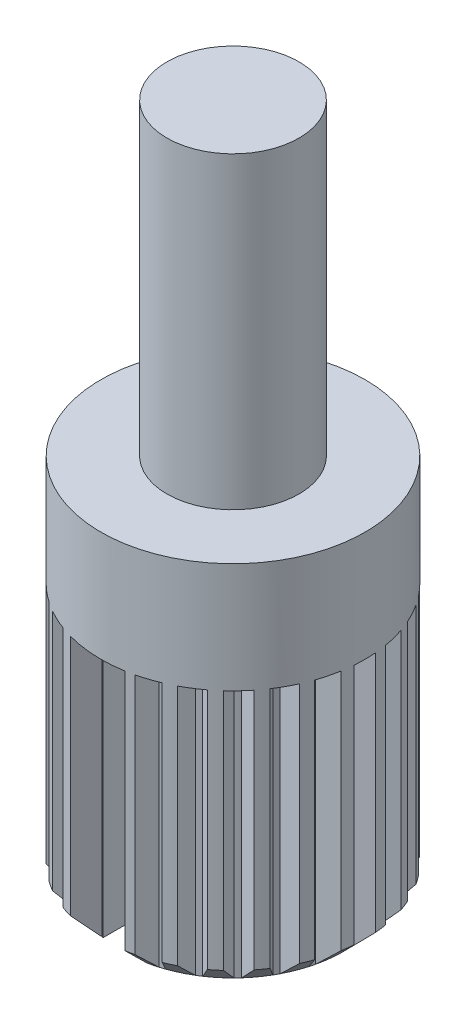
SolidWorks part; units mm, degrees
ref_plane "Alzado" through (0, 0, 0) normal (0, 0, 1) x (1, 0, 0)
ref_plane "Planta" through (0, 0, 0) normal (0, 1, 0) x (1, 0, 0)
ref_plane "Vista lateral" through (0, 0, 0) normal (1, 0, 0) x (0, 0, -1)
sketch "Croquis1" plane through (0, 0, 0) normal (0, 1, 0) x (1, 0, 0)
  circle A0 centre (0, 0) radius 1.5
extrude "Saliente-Extruir1" add sketch "Croquis1" along normal blind 7
sketch "Croquis2" plane through (0, 0, 0) normal (0, -1, 0) x (1, 0, 0)
  circle A0 centre (0, 0) radius 3
extrude "Saliente-Extruir2" add sketch "Croquis2" along normal blind 8.5
fillet "Chaflán1" radius 0.5 1 edges at (0, -8.5, -3) type face fillet profile chamfer first side face at (0, -8.5, -3) second side face at (0, -8.5, -3)
sketch "Croquis3" plane through (0, -8.5, 0) normal (0, -1, 0) x (1, 0, 0)
  line L1 (0.5, 3.3575) -> (-0.5, 3.3575)
  line L2 (0.5, 3.3575) -> (0.5, -3.8145)
  line L3 (-0.5, 3.3575) -> (-0.5, -3.8145)
  line L4 (-0.5, -3.8145) -> (0.5, -3.8145)
  point P4 (0, 0)
extrude "Cortar-Extruir1" cut sketch "Croquis3" against normal blind 6
sketch "Croquis4" plane through (0, -8.5, 0) normal (0, -1, 0) x (1, 0, 0)
  line L0 (3.25, 0) -> (3.2525, 0)
  line L1 (3, 0.25) -> (2.4993, 0.06)
  line L3 (3, -0.25) -> (2.4993, -0.06)
  arc A0 (3, -0.25) -> (3, 0.25) centre (3, 0) ccw
  arc A2 (2.4993, -0.06) -> (2.4993, 0.06) centre (0, 0) ccw
  arc A3 (0.5, -2.958) -> (0.5, 2.958) centre (0, 0) ccw construction
extrude "Cortar-Extruir5" cut sketch "Croquis4" against normal blind 6 contours A0 L1 A2 L3
pattern_circular "MatrizC1" count 25 over 360 about axis through (0, -8.5, 0) along (0, 1, 0) of "Cortar-Extruir5"
